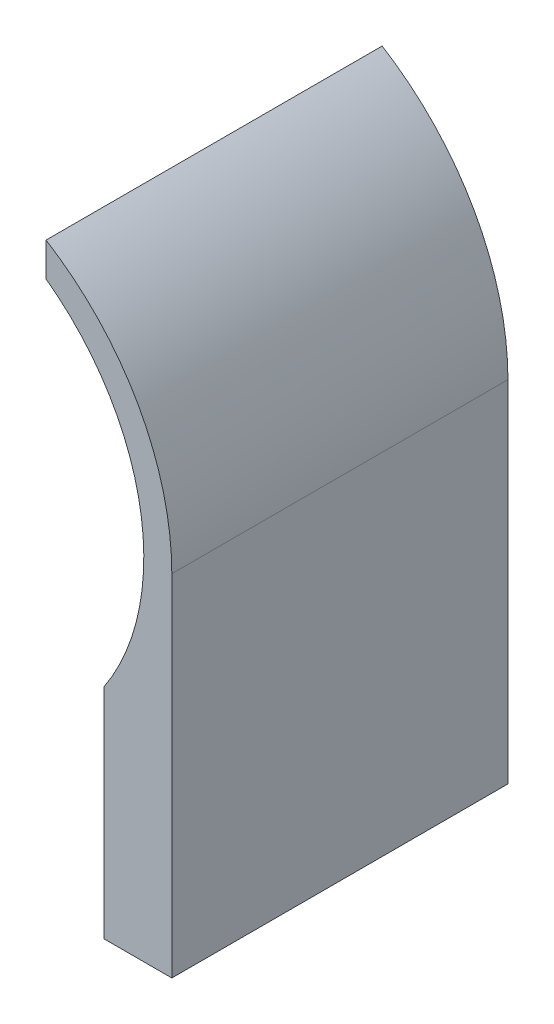
SolidWorks part; units mm, degrees
material "201 Annealed Stainless Steel (SS)"
ref_plane "Front Plane" through (0, 0, 0) normal (0, 0, 1) x (1, 0, 0)
ref_plane "Top Plane" through (0, 0, 0) normal (0, 1, 0) x (1, 0, 0)
ref_plane "Right Plane" through (0, 0, 0) normal (1, 0, 0) x (0, 0, -1)
sketch "Sketch2" plane through (0, 0, 0) normal (0, 0, 1) x (1, 0, 0)
  line L0 (-81.7487, 0) -> (129.7647, 0) construction
  line L1 (0, 82.2046) -> (0, -95) construction
  line L2 (50.1, 0) -> (50.1, 106.5165) construction
  line L3 (-70.7312, -47.1391) -> (70.7312, -47.1391) construction
  line L4 (70.7312, -47.1391) -> (70.7312, -125)
  line L5 (95, 0) -> (95, -125)
  line L6 (95, -125) -> (70.7312, -125)
  line L7 (50.1, 80.7155) -> (50.1, 68.6658)
  line L8 (0, -95) -> (0, -125) construction
  line L9 (0, -125) -> (111.0903, -125) construction
  circle A0 centre (0, 0) radius 85 construction
  circle A1 centre (0, 0) radius 95 construction
  arc A2 (50.1, 68.6658) -> (70.7312, -47.1391) centre (0, 0) cw
  arc A3 (95, 0) -> (50.1, 80.7155) centre (0, 0) ccw
  dimension "D1" = 170
  dimension "D2" = 190
  dimension "D5" = 30
  dimension "D3" = 50.1
  dimension "D4" = 167.1
extrude "Inner Ring - Right Side" add sketch "Sketch2" along normal blind 120
